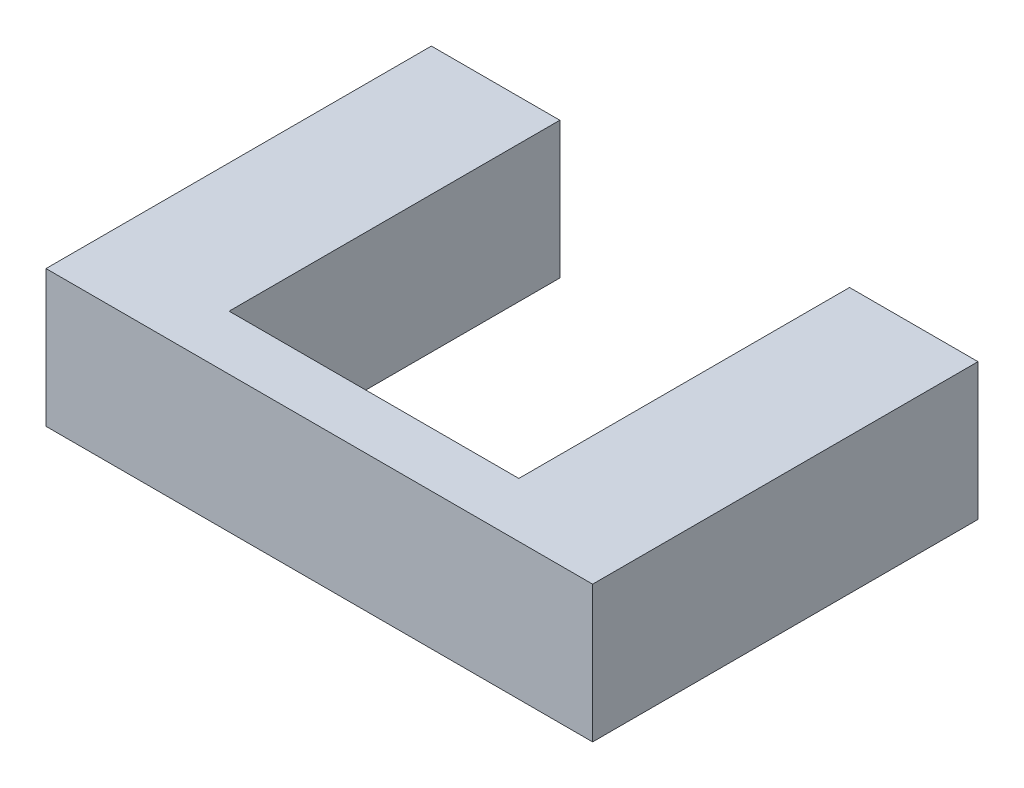
SolidWorks part; units mm, degrees
ref_plane "Front Plane" through (0, 0, 0) normal (0, 0, 1) x (1, 0, 0)
ref_plane "Top Plane" through (0, 0, 0) normal (0, 1, 0) x (1, 0, 0)
ref_plane "Right Plane" through (0, 0, 0) normal (1, 0, 0) x (0, 0, -1)
sketch "Sketch1" plane through (0, 0, 0) normal (0, 1, 0) x (1, 0, 0)
  line L1 (-25.4, 17.907) -> (25.4, 17.907)
  line L2 (-25.4, 17.907) -> (-25.4, -17.907)
  line L3 (-25.4, -17.907) -> (25.4, -17.907)
  line L4 (25.4, 17.907) -> (25.4, -17.907)
  line L5 (-25.4, 17.907) -> (25.4, -17.907) construction
  line L6 (-25.4, -17.907) -> (25.4, 17.907) construction
  point P0 (0, 0)
  dimension "D1" = 35.814
  dimension "D2" = 50.8
extrude "Boss-Extrude1" add sketch "Sketch1" along normal blind 12.7
sketch "Sketch2" plane through (0, 12.7, 0) normal (0, 1, 0) x (1, 0, 0)
  line L0 (25.4, 17.907) -> (-25.4, 17.907) construction
  line L1 (13.462, 17.907) -> (-13.462, 17.907)
  line L2 (13.462, 17.907) -> (13.462, -12.827)
  line L3 (13.462, -12.827) -> (-13.462, -12.827)
  line L4 (-13.462, 17.907) -> (-13.462, -12.827)
  line L5 (25.4, -17.907) -> (25.4, 17.907) construction
  dimension "D1" = 26.924
  dimension "D2" = 30.734
  dimension "D3" = 11.938
extrude "Cut-Extrude1" cut sketch "Sketch2" against normal blind 12.7
